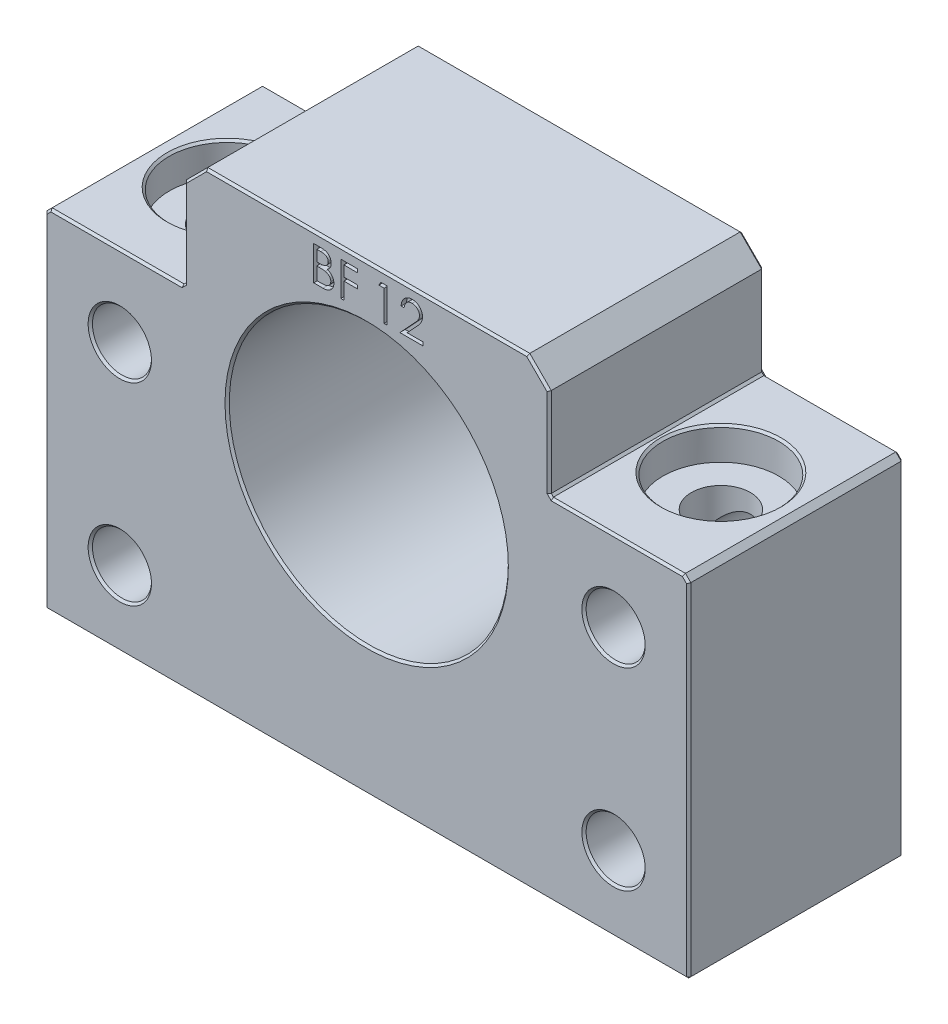
SolidWorks part; units mm, degrees
ref_plane "Front" through (0, 0, 0) normal (0, 0, 1) x (1, 0, 0)
ref_plane "Top" through (0, 0, 0) normal (0, 1, 0) x (1, 0, 0)
ref_plane "Right" through (0, 0, 0) normal (1, 0, 0) x (0, 0, -1)
sketch "Sketch2" plane through (0, 0, 0) normal (0, 0, 1) x (1, 0, 0)
  line L0 (30, -25) -> (-30, -25)
  line L1 (-30, -25) -> (-30, 7.5)
  line L2 (-30, 7.5) -> (-17, 7.5)
  line L3 (-17, 7.5) -> (-17, 18)
  line L4 (-17, 18) -> (17, 18)
  line L5 (0, 18) -> (0, -25) construction
  line L6 (17, 7.5) -> (17, 18)
  line L7 (30, 7.5) -> (17, 7.5)
  line L8 (30, -25) -> (30, 7.5)
  circle A0 centre (0, 0) radius 13
  circle A1 centre (-23, 0) radius 2.75
  circle A2 centre (23, 0) radius 2.75
  circle A3 centre (-23, -18) radius 2.75
  circle A4 centre (23, -18) radius 2.75
  circle A5 centre (23, 0) radius 2.75
  dimension "D3" = 25
  dimension "D9" = 5.5
  dimension "D10" = 26
  dimension "D1" = 60
  dimension "D2" = 32.5
  dimension "D4" = 34
  dimension "D5" = 43
  dimension "D6" = 2
  dimension "D7" = 46
  dimension "D8" = 18
extrude "Boss-Extrude1" add sketch "Sketch2" against normal blind 20 contours L5 L4 L3 L2 L1 L0 A0 A1 A3 | L4 L5 A0 L0 L8 L7 L6 A4 A2 region at (16.1623, -6.9335, 0) region at (-16.1623, -6.9335, 0)
chamfer "Chamfer1" distance 2 angle 45 2 edges at (17, 18, -10) (-17, 18, -10)
sketch "Sketch7" plane through (0, 7.5, 0) normal (0, 1, 0) x (1, 0, 0)
  line L0 (0, 20) -> (0, 0) construction
  line L1 (-15, 20) -> (15, 20) construction
  line L2 (-30, 10) -> (-17, 10) construction
  line L3 (-30, 20) -> (-30, 0) construction
  line L4 (-17, 20) -> (-17, 0) construction
  circle A0 centre (-23, 10) radius 2.75
  circle A1 centre (23, 10) radius 2.75
  dimension "D1" = 5.5
  dimension "D2" = 46
extrude "Cut-Extrude4" cut sketch "Sketch7" against normal through all
sketch "Sketch8" plane through (0, 7.5, 0) normal (0, 1, 0) x (1, 0, 0)
  line L0 (0, 20) -> (0, 0) construction
  line L1 (-15, 20) -> (15, 20) construction
  line L2 (-15, 0) -> (15, 0) construction
  circle A0 centre (-23, 10) radius 5.4
  circle A1 centre (23, 10) radius 5.4
  dimension "D1" = 10.8
extrude "Cut-Extrude5" cut sketch "Sketch8" against normal blind 3
chamfer "Chamfer4" distance 0.2 angle 45 38 edges at (-23, -25, -7.25) (23, -25, -12.75) (25.75, 0, -20) (25.75, -18, -20) (-20.25, -18, -20) (-20.25, 0, -20) (13, 0, -20) (25.75, 0, 0) (25.75, -18, 0) (-20.25, -18, 0) (-20.25, 0, 0) (13, 0, 0) (30, -25, -10) (-30, -25, -10) (-16, 17, -20) (-17, 11.75, -20) (-23.5, 7.5, -20) (-30, -8.75, -20) (0, -25, -20) (30, -8.75, -20) (23.5, 7.5, -20) (0, 18, -20) (16, 17, -20) (17, 11.75, -20) (23.5, 7.5, 0) (30, -8.75, 0) (0, -25, 0) (-30, -8.75, 0) (-23.5, 7.5, 0) (-17, 7.5, -10) (-17, 11.75, 0) (-16, 17, 0) (0, 18, 0) (16, 17, 0) (17, 11.75, 0) (17, 7.5, -10) (23, 7.5, -15.4) (-23, 7.5, -4.6)
chamfer "Chamfer5" distance 0.5 angle 45 2 edges at (30, 7.5, -10) (-30, 7.5, -10)
chamfer "Chamfer6" distance 0.2 angle 45 4 edges at (29.75, 7.25, -20) (-29.75, 7.25, -20) (-29.75, 7.25, 0) (29.75, 7.25, 0)
sketch "Sketch9" plane through (0, 0, 0) normal (0, 0, 1) x (1, 0, 0)
  line L0 (-5.3379, 13.8241) -> (4.5319, 13.8241) construction
  line L1 (0, 17.8) -> (0, 13.2) construction
  line L2 (14.9172, 17.8) -> (-14.9172, 17.8) construction
  circle A0 centre (0, 0) radius 13.2 construction
  text T0 "BF 12" font "Century Gothic" height in points 12
extrude "Cut-Extrude6" cut sketch "Sketch9" against normal blind 0.5
